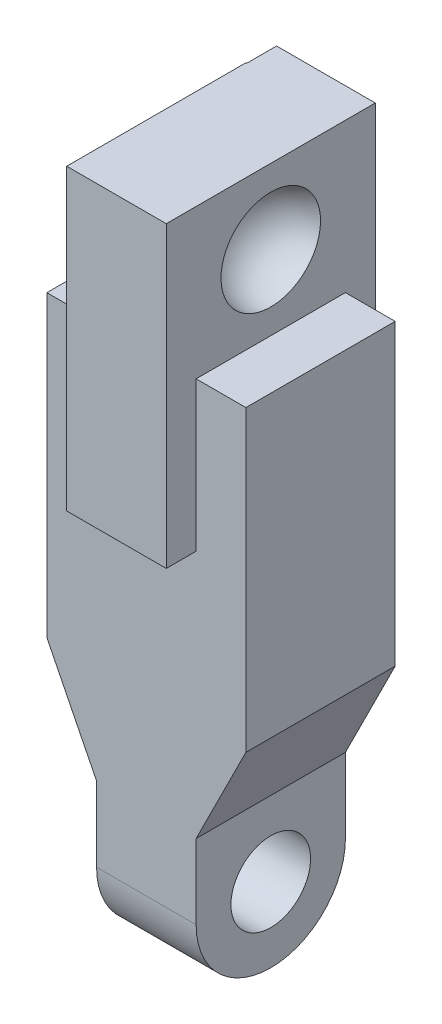
SolidWorks part; units mm, degrees
ref_plane "Front Plane" through (0, 0, 0) normal (0, 0, 1) x (1, 0, 0)
ref_plane "Top Plane" through (0, 0, 0) normal (0, 1, 0) x (1, 0, 0)
ref_plane "Right Plane" through (0, 0, 0) normal (1, 0, 0) x (0, 0, -1)
sketch "Sketch1" plane through (0, 0, 0) normal (0, 0, 1) x (1, 0, 0)
  line L1 (-4.878, 6.0772) -> (5.122, 6.0772)
  line L2 (-4.878, 6.0772) -> (-4.878, -23.9228)
  line L3 (-4.878, -23.9228) -> (5.122, -23.9228)
  line L4 (5.122, 6.0772) -> (5.122, -23.9228)
  dimension "D1" = 10
  dimension "D2" = 30
extrude "Boss-Extrude1" add sketch "Sketch1" along normal blind 15 contours L2 L1 L4 L3
sketch "Sketch2" plane through (0, 0, 15) normal (0, 0, 1) x (1, 0, 0)
  line L0 (-9.878, -8.9228) -> (-4.878, -8.9228)
  line L1 (-4.878, -48.9228) -> (-9.878, -38.9228)
  line L2 (-4.878, 6.0772) -> (-4.878, -23.9228) construction
  line L4 (-9.878, -8.9228) -> (-9.878, -38.9228)
  line L6 (10.122, -8.9228) -> (10.122, -38.9228)
  line L7 (-4.878, -8.9228) -> (-4.878, -23.9228)
  line L8 (-4.878, -23.9228) -> (5.122, -23.9228)
  line L9 (5.122, -23.9228) -> (5.122, -8.9228)
  line L10 (5.122, 6.0772) -> (5.122, -23.9228) construction
  line L11 (5.122, -8.9228) -> (10.122, -8.9228)
  line L13 (-4.878, -48.9228) -> (5.122, -48.9228)
  line L15 (5.122, -48.9228) -> (10.122, -38.9228)
  dimension "D1" = 5
  dimension "D2" = 5
  dimension "D3" = 30
sketch "Sketch3" plane through (0, 0, 15) normal (0, 0, 1) x (1, 0, 0)
extrude "Boss-Extrude5" add sketch "Sketch2" against normal blind 15 contours L13 L15 L6 L11 L2 L0 L4 L1 | L1 L4 L0 L7 L8 L9 L11 L6 L15 L13 region at (0.122, -30.6589, 15)
sketch "Sketch5" plane through (0, 0, 15) normal (0, 0, 1) x (1, 0, 0)
sketch "Sketch6" plane through (0, 0, 15) normal (0, 0, 1) x (1, 0, 0)
  line L1 (-4.878, 6.0772) -> (5.122, 6.0772)
  line L2 (-4.878, 6.0772) -> (-4.878, -23.9228)
  line L3 (-4.878, -23.9228) -> (5.122, -23.9228)
  line L4 (5.122, 6.0772) -> (5.122, -23.9228)
  dimension "D1" = 30
  dimension "D2" = 10
sketch "Sketch7" plane through (0, 0, 0) normal (0, 0, -1) x (-1, 0, 0)
  line L3 (-5.122, 6.0772) -> (4.7948, 6.0772)
  line L4 (-5.122, 6.0772) -> (-5.122, -23.9228)
  line L5 (-5.122, -23.9228) -> (4.7948, -23.9228)
  line L6 (4.7948, 6.0772) -> (4.7948, -23.9228)
  dimension "D1" = 30
extrude "Boss-Extrude7" add sketch "Sketch7" along normal blind 3
sketch "Sketch10" plane through (-4.878, 0, 0) normal (-1, 0, 0) x (0, 0, 1)
  line L1 (7.5, 3.5772) -> (7.5, -6.4228)
  arc A1 (7.5, 3.5772) -> (7.5, -6.4228) centre (7.5, -1.4228) ccw
sketch "Sketch11" plane through (0, 0, 15) normal (0, 0, 1) x (1, 0, 0)
sketch "Sketch12" plane through (0, -48.9228, 0) normal (0, -1, 0) x (1, 0, 0)
  line L1 (-4.878, 15) -> (5.122, 15)
  line L2 (-4.878, 15) -> (-4.878, 0)
  line L3 (-4.878, 0) -> (5.122, 0)
  line L4 (5.122, 15) -> (5.122, 0)
extrude "Boss-Extrude9" add sketch "Sketch12" along normal blind 15
sketch "Sketch13" plane through (-4.878, 0, 0) normal (-1, 0, 0) x (0, 0, 1)
  circle A0 centre (7.5, -56.4228) radius 4
  dimension "D1" = 8
extrude "Cut-Extrude3" cut sketch "Sketch13" against normal blind 15
fillet "Fillet2" radius 7.5 2 edges at (0.122, -63.9228, 0) (0.122, -63.9228, 15)
revolve "Revolve3" add sketch "Sketch10" angle 360 about L1
sketch "Sketch15" plane through (5.122, 0, 0) normal (1, 0, 0) x (0, 0, -1)
  line L0 (-7.5, 3.5772) -> (-7.5, -6.4228)
  arc A0 (-7.5, 3.5772) -> (-7.5, -6.4228) centre (-7.5, -1.4228) ccw
  dimension "D1" = 10
revolve "Cut-Revolve1" cut sketch "Sketch15" angle 360 about L0
extrude "Boss-Extrude11" add sketch "Sketch6" along normal blind 3
